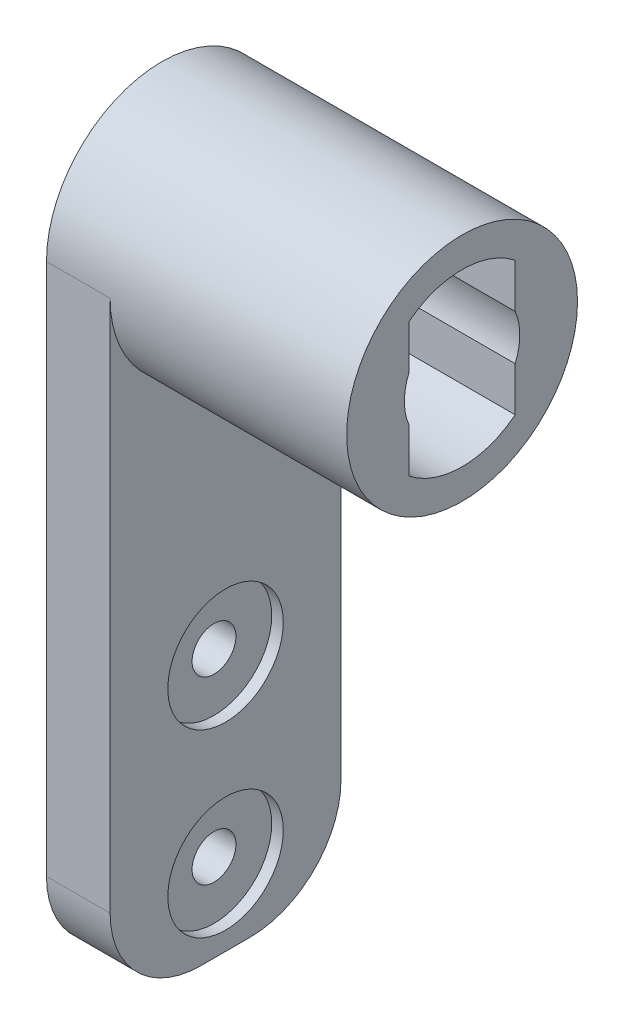
SolidWorks part; units mm, degrees
material "ABS"
ref_plane "Front Plane" through (0, 0, 0) normal (1, 0, 0) x (0, 1, 0)
ref_plane "Top Plane" through (0, 0, 0) normal (0, 0, 1) x (0, 1, 0)
ref_plane "Right Plane" through (0, 0, 0) normal (0, 1, 0) x (-1, 0, 0)
sketch "Sketch1" plane through (0, 0, 0) normal (1, 0, 0) x (0, 1, 0)
  circle A0 centre (0, 0) radius 3.175
  circle A1 centre (0, 0) radius 3
  circle A2 centre (0, 0) radius 6.35
  dimension "D1" = 6
  dimension "D2" = 6.35
  dimension "D3" = 12.7
extrude "Boss-Extrude1" add sketch "Sketch1" along normal blind 16.51 contours A2 A0 region at (0, -6.1704, 0)
ref_plane "Plane1" through (0, 0, 6.35) normal (0, 0, 1) x (0, 1, 0)
sketch "Sketch10" plane through (0, 0, 0) normal (-1, 0, 0) x (0, -1, 0)
  line L0 (0, 6.35) -> (34.29, 6.35)
  line L1 (14.575, 6.35) -> (-14.575, 6.35) construction
  line L2 (34.29, 6.35) -> (34.29, -6.35)
  line L3 (34.29, -6.35) -> (0, -6.35)
  circle A0 centre (0, 0) radius 6.35 construction
  arc A2 (0, 6.35) -> (0, -6.35) centre (0, 0) cw
  dimension "D1" = 34.29
extrude "Boss-Extrude3" add sketch "Sketch10" against normal blind 3.5 contours L0 A2 L3 L2 region at (0, -19.6044, 0)
fillet "Fillet2" radius 5 2 edges at (1.75, -34.29, 6.35) (1.75, -34.29, -6.35)
sketch "Sketch11" plane through (0, 0, 0) normal (-1, 0, 0) x (0, -1, 0)
  line L0 (34.29, 0) -> (0, 0) construction
  line L1 (34.29, 1.35) -> (34.29, -1.35) construction
  circle A0 centre (30.099, 0) radius 1.2065
  circle A1 centre (20.193, 0) radius 1.2065
  dimension "D3" = 2.413
  dimension "D1" = 4.191
  dimension "D2" = 9.906
extrude "Cut-Extrude1" cut sketch "Sketch11" against normal through all
sketch "Sketch12" plane through (3.5, 0, 0) normal (1, 0, 0) x (0, 1, 0)
  circle A0 centre (-20.193, 0) radius 3.175
  circle A1 centre (-30.099, 0) radius 3.175
  dimension "D1" = 6.35
extrude "Cut-Extrude2" cut sketch "Sketch12" against normal blind 0.635
sketch "Sketch13" plane through (16.51, 0, 0) normal (1, 0, 0) x (0, 1, 0)
  line L1 (-3.6808, -2.921) -> (3.6808, -2.921)
  line L2 (-3.6808, -2.921) -> (-3.6808, 2.921)
  line L3 (-3.6808, 2.921) -> (3.6808, 2.921)
  line L4 (3.6808, -2.921) -> (3.6808, 2.921)
  line L5 (-3.6808, -2.921) -> (3.6808, 2.921) construction
  line L6 (-3.6808, 2.921) -> (3.6808, -2.921) construction
  circle A0 centre (0, 0) radius 4.699
  circle M5 centre (0, 0) radius 3.175
  dimension "D1" = 9.398
  dimension "D2" = 5.842
extrude "Cut-Extrude3" cut sketch "Sketch13" against normal blind 10.16 contours L2 A0 | L3 L1 M5 | L3 L2 L1 M5 | L1 L4 L3 M5 | L4 A0 region at (16.51, -3.6175, 0) region at (16.51, -4.0921, 0) region at (16.51, 0, 0) region at (16.51, 2.4626, -2.8577) region at (16.51, 4.0921, 0)
